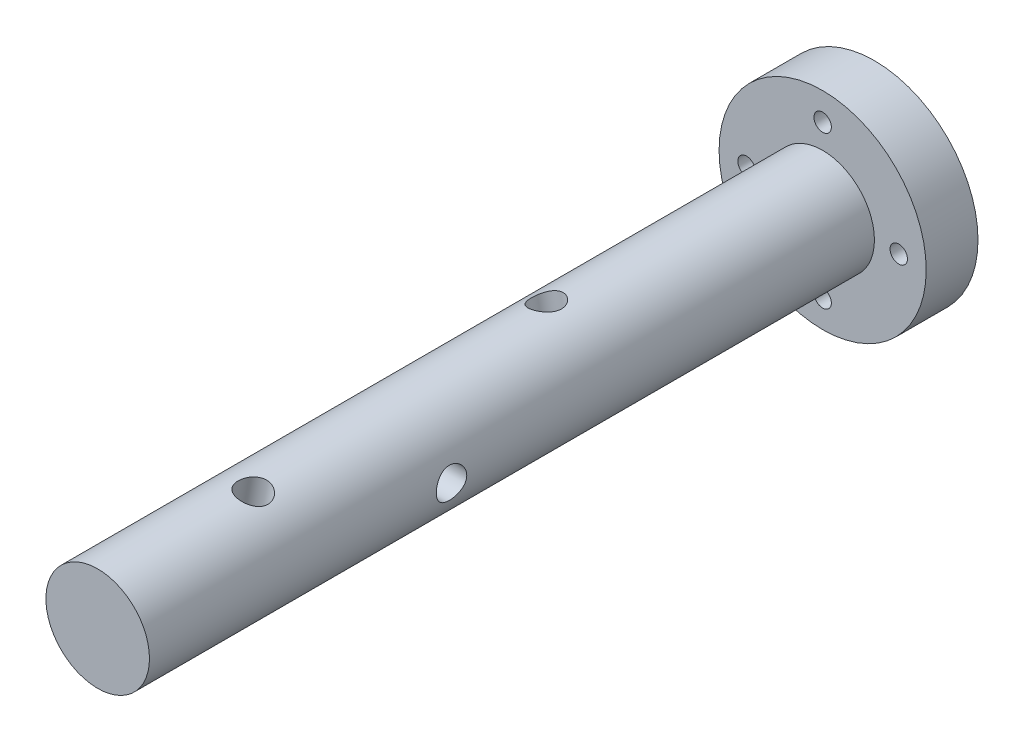
SolidWorks part; units mm, degrees
ref_plane "Front Plane" through (0, 0, 0) normal (0, 0, 1) x (1, 0, 0)
ref_plane "Top Plane" through (0, 0, 0) normal (0, 1, 0) x (1, 0, 0)
ref_plane "Right Plane" through (0, 0, 0) normal (1, 0, 0) x (0, 0, -1)
sketch "Sketch1" plane through (0, 0, 0) normal (0, 0, 1) x (1, 0, 0)
  circle A0 centre (0, 0) radius 4.7625
  circle A1 centre (0, 0) radius 9.525
  circle A2 centre (0, 0) radius 3.175
  circle A3 centre (0, 7) radius 0.8
  circle A4 centre (7, 0) radius 0.8
  circle A5 centre (0, 0) radius 3.175
  circle A6 centre (0, -7) radius 0.8
  circle A7 centre (0, 0) radius 3.175
  circle A8 centre (-7, 0) radius 0.8
  circle A9 centre (0, 0) radius 3.175
  point P19 (0, 0)
  dimension "D1" = 9.525
  dimension "D2" = 19.05
  dimension "D3" = 6.35
  dimension "D5" = 1.6
  dimension "D4" = 7
  dimension "D6" = 4
extrude "Boss-Extrude1" add sketch "Sketch1" along normal blind 66.675 contours A0
extrude "Boss-Extrude2" add sketch "Sketch1<4>" against normal blind 4.7625 contours A1 A8 A6 A4 A3 A0 | A0 A2 region at (-4.6278, 0, 0) region at (-9.2556, 0, 0)
sketch "Sketch1<4>" plane through (0, 0, 0) normal (0, 0, 1) x (1, 0, 0) same geometry as "Sketch1"
fillet "Fillet1" radius 3.175 1 edges at (3.175, 0, 0)
sketch "Sketch2" plane through (0, 0, 0) normal (0, 1, 0) x (1, 0, 0)
  line L0 (-4.7625, -66.675) -> (4.7625, -66.675) construction
  line L1 (0, -66.675) -> (0, -53.1812) construction
  line L2 (0, -53.1812) -> (0, -38.8937) construction
  line L3 (0, -38.8937) -> (0, -24.6062) construction
  dimension "D2" = 13.4937
  dimension "D1" = 14.2875
  dimension "D3" = 14.2875
sketch "Sketch3" plane through (0, 0, 0) normal (1, 0, 0) x (0, 0, -1)
  circle A0 centre (-38.8937, 0) radius 1.4
  dimension "D1" = 2.8
extrude "Cut-Extrude2" cut sketch "Sketch3" against normal through all both and the other way through all
ref_plane "Plane1" through (0, 0, 0) normal (0.1736, 0.9848, 0) x (0, 0, -1)
ref_plane "Plane2" through (0, 0, 0) normal (-0.1736, 0.9848, 0) x (0, 0, -1)
sketch "Sketch4" plane through (0, 0, 0) normal (0.1736, 0.9848, 0) x (0, 0, -1)
  circle A0 centre (-53.1812, 0) radius 1.4
  dimension "D1" = 2.8
extrude "Cut-Extrude3" cut sketch "Sketch4" against normal through all both and the other way through all
sketch "Sketch5" plane through (0, 0, 0) normal (-0.1736, 0.9848, 0) x (0, 0, -1)
  circle A0 centre (-24.6062, 0) radius 1.4
  dimension "D1" = 2.8
extrude "Cut-Extrude4" cut sketch "Sketch5" against normal through all both and the other way through all
equation "\"D4@Sketch1\"=7mm"
equation "\"D5@Sketch1\"=1.6mm"
equation "\"normtol\" = 0.01in"
equation "\"loosetol\" = 0.02in"
equation "\"tighttol\" = 0.005in"
equation "\"Fry height\"= 0.5in"
equation "\"Fry spacing\"= 0.5625in"
equation "\"Potato width\"= \"Fry spacing\" * 4"
equation "\"Potato length\"= 80mm"
equation "\"top robot surface separation\" = 0.6875"
equation "\"D2@Sketch2\"=1/4+\"Fry spacing\"/2"
equation "\"D1@Sketch3\"=2.8mm"
equation "\"D1@Sketch2\"=\"Fry spacing\""
equation "\"D3@Sketch2\"=\"Fry spacing\""
equation "\"D1@Sketch4\"=2.8mm"
equation "\"D1@Sketch5\"=2.8mm"
